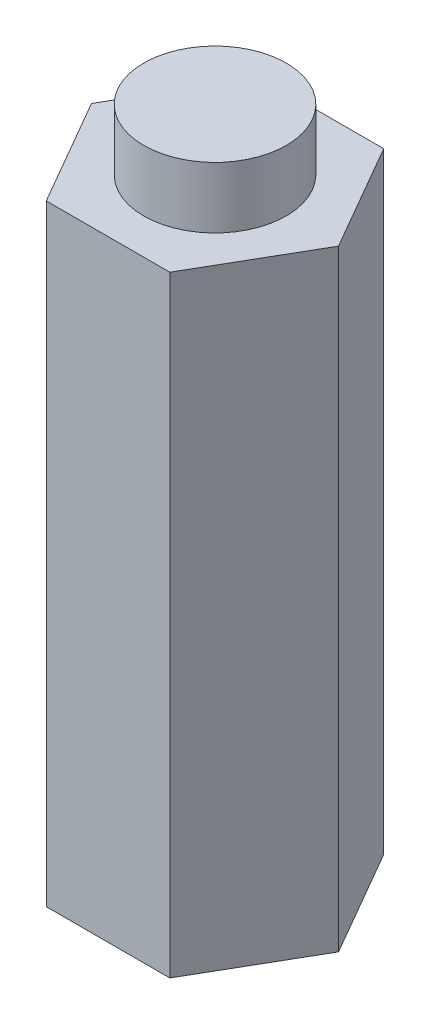
SolidWorks part; units mm, degrees
ref_plane "Front Plane" through (0, 0, 0) normal (0, 0, 1) x (1, 0, 0)
ref_plane "Top Plane" through (0, 0, 0) normal (0, 1, 0) x (1, 0, 0)
ref_plane "Right Plane" through (0, 0, 0) normal (1, 0, 0) x (0, 0, -1)
sketch "Sketch1" plane through (0, 0, 0) normal (0, 1, 0) x (1, 0, 0)
  line L1 (12.1244, 0) -> (6.0622, 10.5)
  line L2 (6.0622, 10.5) -> (-6.0622, 10.5)
  line L3 (-6.0622, 10.5) -> (-12.1244, 0)
  line L4 (-12.1244, 0) -> (-6.0622, -10.5)
  line L5 (-6.0622, -10.5) -> (6.0622, -10.5)
  line L6 (6.0622, -10.5) -> (12.1244, 0)
  circle A0 centre (0, 0) radius 10.5 construction
  circle A1 centre (0, 0) radius 7
  dimension "D1" = 21
extrude "Boss-Extrude1" add sketch "Sketch1" along normal blind 60
extrude "Boss-Extrude2" add sketch "Sketch1<3>" along normal blind 66 contours A1 region at (0, 0, 0)
sketch "Sketch1<3>" plane through (0, 0, 0) normal (0, 1, 0) x (1, 0, 0) same geometry as "Sketch1"
